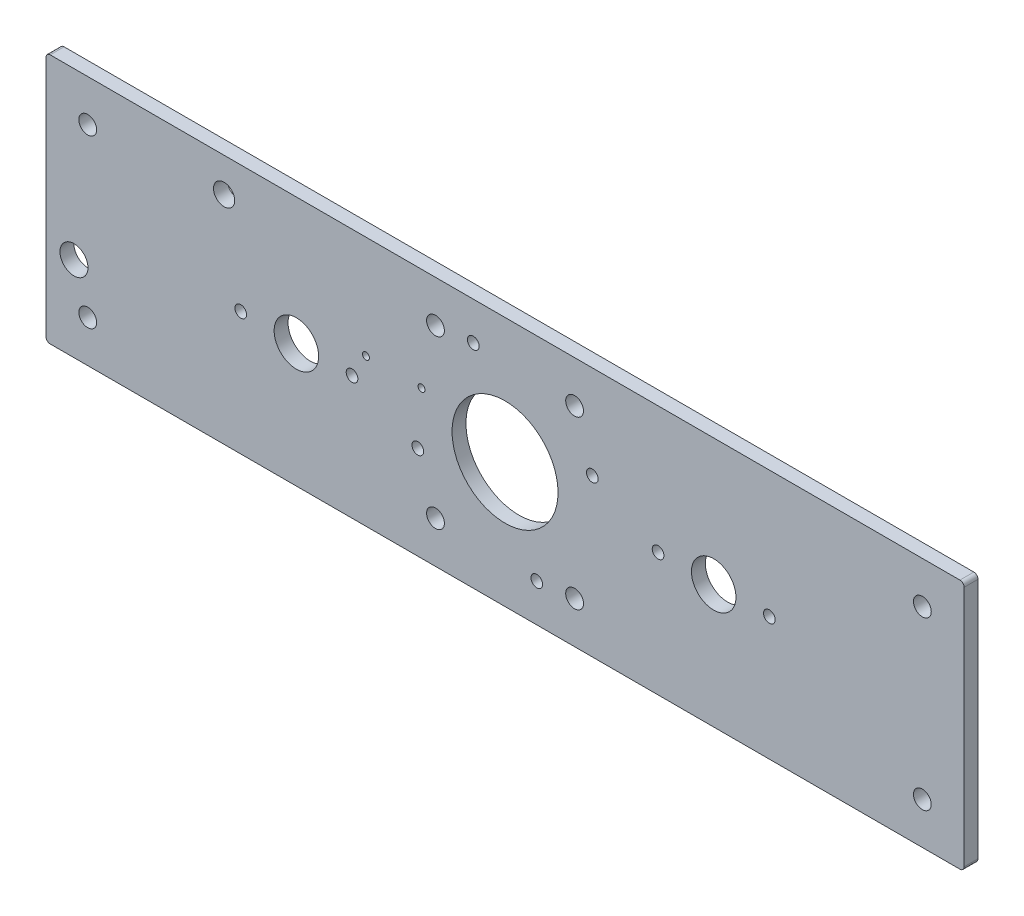
SolidWorks part; units mm, degrees
ref_plane "Front Plane" through (0, 0, 0) normal (0, 0, 1) x (1, 0, 0)
ref_plane "Top Plane" through (0, 0, 0) normal (0, 1, 0) x (1, 0, 0)
ref_plane "Right Plane" through (0, 0, 0) normal (1, 0, 0) x (0, 0, -1)
sketch "Sketch1" plane through (0, 0, 0) normal (0, 0, 1) x (1, 0, 0)
  line L1 (165, -45) -> (-165, -45)
  line L2 (165, -45) -> (165, 45)
  line L3 (165, 45) -> (-165, 45)
  line L4 (-165, -45) -> (-165, 45)
  line L5 (165, -45) -> (-165, 45) construction
  line L6 (165, 45) -> (-165, -45) construction
  circle A0 centre (0, 0) radius 19.05
  point P0 (0, 0)
  dimension "D3" = 38.1
  dimension "D1" = 90
  dimension "D2" = 330
extrude "Boss-Extrude1" add sketch "Sketch1" along normal mid plane 5
hole_wizard "M6 Clearance Hole1" positions "Sketch5" profile "Sketch4" hole size "M6" standard "ANSI Metric" end condition through all
sketch "Sketch5" plane through (0, 0, 2.5) normal (0, 0, 1) x (1, 0, 0)
  line L0 (165, 45) -> (-165, 45) construction
  line L1 (-165, 45) -> (-165, -45) construction
  line L2 (-165, -45) -> (165, -45) construction
  point P0 (-150, 30)
  point P2 (-25, 30)
  point P4 (-25, -30)
  point P6 (-150, -30)
  dimension "D1" = 15
  dimension "D2" = 25
  dimension "D3" = 15
  dimension "D4" = 15
  dimension "D5" = 15
  dimension "D6" = 15
  dimension "D7" = 15
  dimension "D8" = 25
sketch "Sketch4" plane through (-150, 30, 2.5) normal (1, 0, 0) x (0, -1, 0)
  line L0 (0, 0) -> (0, 5)
  line L1 (0, 5) -> (3.2, 5)
  line L2 (3.2, 5) -> (3.2, 0)
  line L5 (3.2, 0) -> (0, 0)
  line L11 (0, -6.35) -> (0, 107.95) construction
  dimension "Thru Hole Dia." = 6.4
  dimension "Thru Hole Depth" = 5
mirror "Mirror2" about plane through (0, 0, 0) normal (1, 0, 0) of "M6 Clearance Hole1"
sketch "Sketch3" plane through (0, 0, 2.5) normal (0, 0, 1) x (1, 0, 0)
  line L0 (0, -0.6) -> (-49.4534, -0.6) construction
  circle A2 centre (-75, -0.6) radius 8
  dimension "D3" = 16
  dimension "D4" = 75
  dimension "D7" = 0.6
extrude "Cut-Extrude2" cut sketch "Sketch3" against normal through all
hole_wizard "M5x0.8 Tapped Hole1" positions "Sketch7" profile "Sketch6" tap size "M5x0.8" standard "ANSI Metric" end condition through all
sketch "Sketch7" plane through (0, 0, 2.5) normal (0, 0, 1) x (1, 0, 0)
  line L0 (-1080, -0.6) -> (48920, -0.6) construction
  circle A0 centre (-75, -0.6) radius 8 construction
  point P0 (-95, -0.6)
  point P2 (-55, -0.6)
  dimension "D1" = 20
  dimension "D2" = 20
sketch "Sketch6" plane through (-95, -0.6, 2.5) normal (1, 0, 0) x (0, -1, 0)
  line L0 (0, 0) -> (0, 5)
  line L1 (0, 5) -> (2.1, 5)
  line L2 (2.1, 5) -> (2.1, 0)
  line L5 (2.1, 0) -> (0, 0)
  line L11 (0, -6.35) -> (0, 107.95) construction
  dimension "Thru Tap Drill Dia." = 4.2
  dimension "Thru Tap Drill Depth" = 5
cosmetic thread "Hole Thread1" parameters "D2"=5
cosmetic thread "Hole Thread2" parameters "D2"=5
mirror "Mirror1" about plane through (0, 0, 0) normal (1, 0, 0) of "M5x0.8 Tapped Hole1", "Cut-Extrude2"
hole_wizard "M5x0.8 Tapped Hole3" positions "Sketch9" profile "Sketch8" tap size "M5x0.8" standard "ANSI Metric" end condition through all
sketch "Sketch9" plane through (0, 0, 2.5) normal (0, 0, 1) x (1, 0, 0)
  line L1 (11.4151, -31.3627) -> (31.3627, 11.4151) construction
  line L2 (11.4151, -31.3627) -> (-31.3627, -11.4151) construction
  line L3 (-31.3627, -11.4151) -> (-11.4151, 31.3627) construction
  line L4 (31.3627, 11.4151) -> (-11.4151, 31.3627) construction
  line L5 (11.4151, -31.3627) -> (-11.4151, 31.3627) construction
  line L6 (-31.3627, -11.4151) -> (31.3627, 11.4151) construction
  line L7 (-1000, 0) -> (49000, 0) construction
  point P1 (-11.4151, 31.3627)
  point P164 (11.4151, -31.3627)
  point P165 (-31.3627, -11.4151)
  point P166 (31.3627, 11.4151)
  dimension "D1" = 47.2
  dimension "D2" = 47.2
  dimension "D3" = 110
  dimension "D4" = 90
  dimension "D5" = 90
  dimension "D6" = 90
  dimension "D7" = 23.6
  dimension "D8" = 23.6
sketch "Sketch8" plane through (-11.4151, 31.3627, 2.5) normal (1, 0, 0) x (0, -1, 0)
  line L0 (0, 0) -> (0, 5)
  line L1 (0, 5) -> (2.1, 5)
  line L2 (2.1, 5) -> (2.1, 0)
  line L5 (2.1, 0) -> (0, 0)
  line L11 (0, -6.35) -> (0, 107.95) construction
  dimension "Thru Tap Drill Dia." = 4.2
  dimension "Thru Tap Drill Depth" = 5
cosmetic thread "Hole Thread3" parameters "D2"=5
cosmetic thread "Hole Thread4" parameters "D2"=5
cosmetic thread "Hole Thread5" parameters "D2"=5
cosmetic thread "Hole Thread6" parameters "D2"=5
fillet "Fillet1" radius 1.5 4 edges at (-165, -45, 0) (165, -45, 0) (165, 45, 0) (-165, 45, 0)
hole_wizard "M3x0.5 Tapped Hole1" positions "Sketch12" profile "Sketch11" tap size "M3x0.5" standard "ANSI Metric" end condition through all
sketch "Sketch12" plane through (0, 0, 2.5) normal (0, 0, 1) x (1, 0, 0)
  line L0 (-50, 8) -> (-30, 8)
  point P0 (-50, 8)
  point P2 (-30, 8)
  dimension "D1" = 20
  dimension "D2" = 8
  dimension "D3" = 30
sketch "Sketch11" plane through (-50, 8, 2.5) normal (1, 0, 0) x (0, -1, 0)
  line L0 (0, 0) -> (0, 5)
  line L1 (0, 5) -> (1.25, 5)
  line L2 (1.25, 5) -> (1.25, 0)
  line L5 (1.25, 0) -> (0, 0)
  line L11 (0, -6.35) -> (0, 107.95) construction
  dimension "Thru Tap Drill Dia." = 2.5
  dimension "Thru Tap Drill Depth" = 5
cosmetic thread "Hole Thread7" parameters "D2"=3
cosmetic thread "Hole Thread8" parameters "D2"=3
sketch "Sketch13" plane through (0, 0, 2.5) normal (0, 0, 1) x (1, 0, 0)
  circle A0 centre (-100.9899, 32.7821) radius 3.8128
extrude "Cut-Extrude3" cut sketch "Sketch13" against normal through all
sketch "Sketch14" plane through (0, 0, 2.5) normal (0, 0, 1) x (1, 0, 0)
  circle A0 centre (-154.9448, -14.5073) radius 5.0278
extrude "Cut-Extrude4" cut sketch "Sketch14" against normal blind 10
equation "\"D4@Sketch3\"=150/2"
